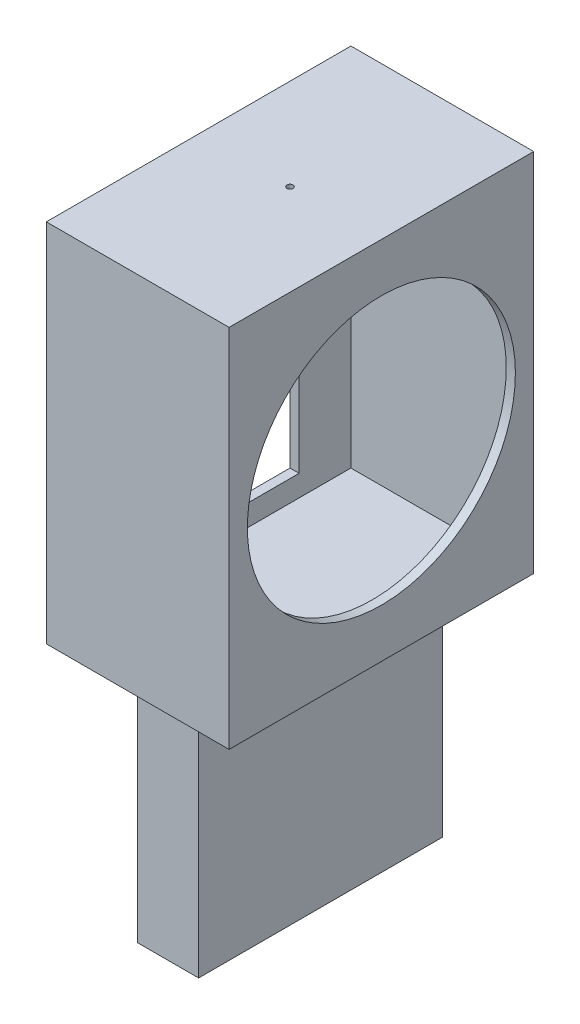
SolidWorks part; units mm, degrees
ref_plane "Front Plane" through (0, 0, 0) normal (0, 0, 1) x (1, 0, 0)
ref_plane "Top Plane" through (0, 0, 0) normal (0, 1, 0) x (1, 0, 0)
ref_plane "Right Plane" through (0, 0, 0) normal (1, 0, 0) x (0, 0, -1)
other "Configuration Table"
sketch "Sketch1" plane through (0, 0, 0) normal (1, 0, 0) x (0, 0, -1)
  line L1 (50, 80) -> (-50, 80)
  line L2 (50, 80) -> (50, 200)
  line L3 (50, 200) -> (-50, 200)
  line L4 (-50, 80) -> (-50, 200)
  line L5 (50, 80) -> (-50, 200) construction
  line L6 (50, 200) -> (-50, 80) construction
  point P0 (0, 140)
extrude "outer" add sketch "Sketch1" along normal blind 60 from offset 98 separate body
sketch "Sketch2" plane through (0, 0, 0) normal (1, 0, 0) x (0, 0, -1)
  line L1 (47, 83) -> (-47, 83)
  line L2 (47, 83) -> (47, 197)
  line L3 (47, 197) -> (-47, 197)
  line L4 (-47, 83) -> (-47, 197)
  line L5 (47, 83) -> (-47, 197) construction
  line L6 (47, 197) -> (-47, 83) construction
  point P0 (0, 140)
extrude "inner" add sketch "Sketch2" along normal blind 54 from offset 101 separate body
sketch "Sketch3" plane through (0, 0, 0) normal (1, 0, 0) x (0, 0, -1)
  line L1 (30, 90) -> (-30, 90)
  line L2 (30, 90) -> (30, 190)
  line L3 (30, 190) -> (-30, 190)
  line L4 (-30, 90) -> (-30, 190)
  line L5 (30, 90) -> (-30, 190) construction
  line L6 (30, 190) -> (-30, 90) construction
  point P0 (0, 140)
extrude "throat_port" add sketch "Sketch3" along normal blind 5 from offset 97 separate body
sketch "Sketch4" plane through (0, 0, 0) normal (1, 0, 0) x (0, 0, -1)
  circle A0 centre (0, 140) radius 44
extrude "fan_port" add sketch "Sketch4" along normal blind 5 from offset 154 separate body
sketch "Sketch5" plane through (0, 0, 0) normal (0, 1, 0) x (1, 0, 0)
  circle A0 centre (128, 0) radius 1
extrude "tc_port" add sketch "Sketch5" along normal blind 5 from offset 196 separate body
combine bodies "Combine1" operation type subtract main body 102 bodies to subtract 103
combine bodies "Combine2" operation type subtract main body 107 bodies to subtract 104
combine bodies "Combine3" operation type subtract main body 108 bodies to subtract 105
combine bodies "Combine4" operation type subtract main body 109 bodies to subtract 106
sketch "Sketch6" plane through (0, 0, 0) normal (1, 0, 0) x (0, 0, -1)
  line L0 (-50, 80) -> (50, 80) construction
  line L1 (40, 0) -> (-40, 0)
  line L2 (40, 0) -> (40, 80)
  line L3 (40, 80) -> (-40, 80)
  line L4 (-40, 0) -> (-40, 80)
  line L5 (40, 0) -> (-40, 80) construction
  line L6 (40, 80) -> (-40, 0) construction
  point P0 (0, 40)
extrude "plenum_stand" add sketch "Sketch6" along normal blind 20 from offset 118 separate body
